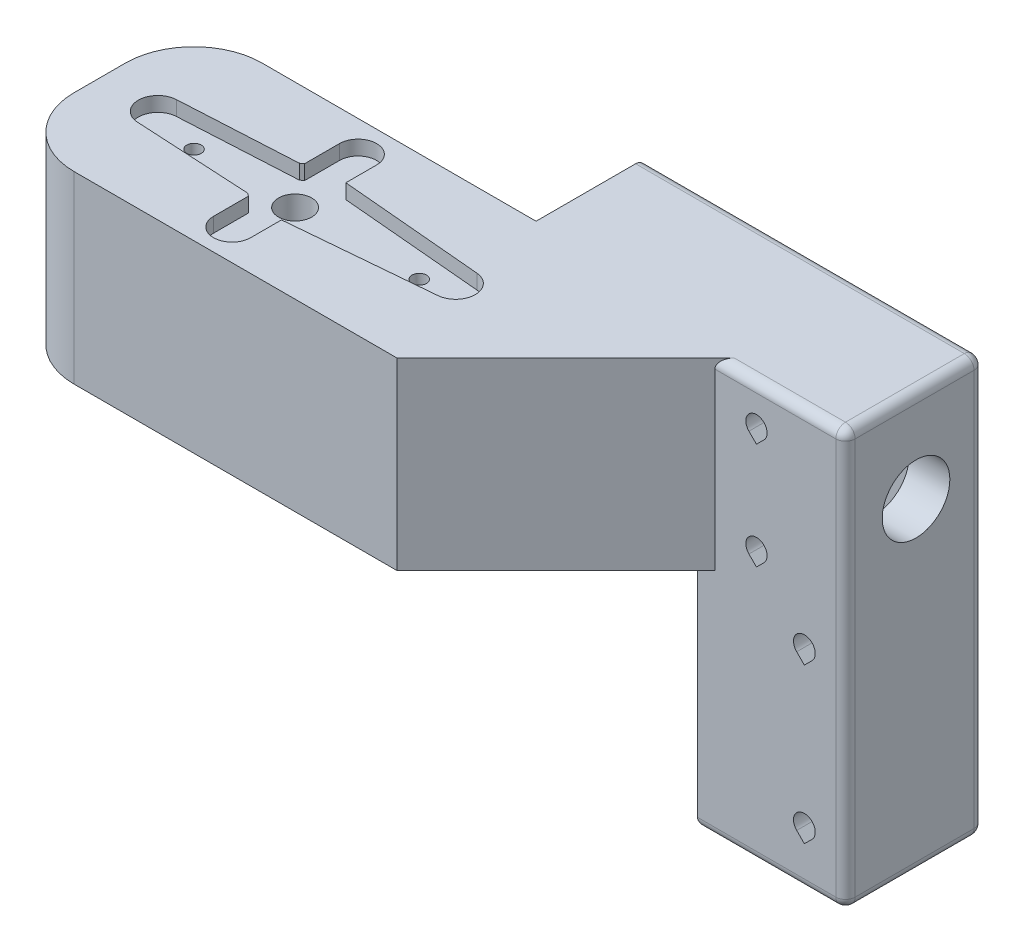
SolidWorks part; units mm, degrees
material "PVC Rígido"
ref_plane "Plano frontal" through (0, 0, 0) normal (0, 0, 1) x (1, 0, 0)
ref_plane "Plano superior" through (0, 0, 0) normal (0, 1, 0) x (1, 0, 0)
ref_plane "Plano direito" through (0, 0, 0) normal (1, 0, 0) x (0, 0, -1)
sketch "Esboço1" plane through (0, 0, 0) normal (0, 1, 0) x (1, 0, 0)
  line L0 (0, 0) -> (-14.05, 0) construction
  line L1 (-14.1591, 1.997) -> (-2.2091, 2.65)
  line L2 (-2.2091, -2.65) -> (-14.1591, -1.997)
  arc A0 (-2.2091, -2.65) -> (-2.2091, 2.65) centre (0, 0) ccw
  arc A1 (-14.1591, 1.997) -> (-14.1591, -1.997) centre (-14.05, 0) ccw
  dimension "D1" = 6.9
  dimension "D2" = 4
  dimension "D3" = 19.5
  dimension "D4" = 5.3
extrude "Ressalto-extrusão1" add sketch "Esboço1" against normal blind 1.4
sketch "Esboço2" plane through (0, -1.4, 0) normal (0, -1, 0) x (1, 0, 0)
  arc A0 (-2.2091, -2.65) -> (-2.2091, 2.65) centre (0, 0) ccw construction
  circle A1 centre (0, 0) radius 3.45
extrude "Ressalto-extrusão2" add sketch "Esboço2" along normal offset from surface (2.4 mm away) 3.8 up to face at (-7.242, 0, 0)
hole_wizard "Furo1" positions "Esboço9" profile "Esboço10" legacy end condition through all
sketch "Esboço9" plane through (0, 0, 0) normal (0, 1, 0) x (1, 0, 0)
  line L1 (-14.45, 0) -> (0, 0) construction
  arc A2 (-14.1591, 1.997) -> (-14.1591, -1.997) centre (-14.05, 0) ccw construction
  point P0 (-14.45, 0)
  point P19 (-16.05, 0)
  dimension "D1" = 1.6
sketch "Esboço10" plane through (-14.45, 0, 0) normal (1, 0, 0) x (0, 0, 1)
  line L0 (0, 0) -> (0, 3.8)
  line L1 (0, 3.8) -> (0.6, 3.8)
  line L2 (0.6, 3.8) -> (0.6, 0)
  line L3 (0.6, 0) -> (0, 0)
  line L4 (0, 110) -> (0, -10) construction
  dimension "Diameter" = 1.2
  dimension "Depth" = 3.8
pattern_linear "Padrão linear1" count 6 spacing 2 along (1, 0, 0) of "Furo1"
sketch "Esboço12" plane through (0, 0, 0) normal (0, 1, 0) x (1, 0, 0)
  line L0 (0.3041, 3.4366) -> (16.6263, 1.9922)
  line L1 (16.6263, -1.9922) -> (0.3041, -3.4366)
  arc A0 (-2.2091, -2.65) -> (-2.2091, 2.65) centre (0, 0) ccw construction
  arc A1 (0.3041, -3.4366) -> (0.3041, 3.4366) centre (0, 0) ccw
  arc A2 (16.6263, 1.9922) -> (16.6263, -1.9922) centre (16.45, 0) cw
  arc A3 (-14.1591, 1.997) -> (-14.1591, -1.997) centre (-14.05, 0) ccw construction
  dimension "D1" = 2
  dimension "D2" = 34.5
extrude "Ressalto-extrusão3" add sketch "Esboço12" against normal up to surface (1.4 mm away) up to face at (-12.45, -1.4, 0.6)
hole_wizard "Furo2" positions "Esboço13" profile "Esboço14" legacy end condition through all
sketch "Esboço13" plane through (0, 0, 0) normal (0, 1, 0) x (1, 0, 0)
  line L0 (0, 0) -> (16.85, 0) construction
  arc A0 (16.6263, -1.9922) -> (16.6263, 1.9922) centre (16.45, 0) ccw construction
  point P0 (16.85, 0)
  point P6 (18.45, 0)
  dimension "D1" = 1.6
sketch "Esboço14" plane through (16.85, 0, 0) normal (1, 0, 0) x (0, 0, 1)
  line L0 (0, 0) -> (0, 3.8)
  line L1 (0, 3.8) -> (0.6, 3.8)
  line L2 (0.6, 3.8) -> (0.6, 0)
  line L3 (0.6, 0) -> (0, 0)
  line L4 (0, 110) -> (0, -10) construction
  dimension "Diameter" = 1.2
  dimension "Depth" = 3.8
pattern_linear "Padrão linear2" count 7 spacing 2 along (-1, 0, 0) of "Furo2"
sketch "Esboço16" plane through (0, 0, 0) normal (0, 1, 0) x (1, 0, 0)
  line L0 (0, -6.45) -> (0, 6.45) construction
  line L1 (-1.9, -6.45) -> (-1.9, 6.45)
  line L2 (1.9, -6.45) -> (1.9, 6.45)
  arc A0 (-1.9, -6.45) -> (1.9, -6.45) centre (0, -6.45) ccw
  arc A1 (1.9, 6.45) -> (-1.9, 6.45) centre (0, 6.45) ccw
  point P2 (0, 0)
  dimension "D2" = 16.7
  dimension "D1" = 3.8
extrude "Ressalto-extrusão4" add sketch "Esboço16" against normal up to surface (1.4 mm away) up to face at (14.85, -1.4, 0.6)
hole_wizard "Furo3" positions "Esboço17" profile "Esboço18" legacy end condition through all
sketch "Esboço17" plane through (0, 0, 0) normal (0, 1, 0) x (1, 0, 0)
  point P0 (0, -6.45)
sketch "Esboço18" plane through (0, 0, 6.45) normal (1, 0, 0) x (0, 0, 1)
  line L0 (0, 0) -> (0, 3.8)
  line L1 (0, 3.8) -> (0.6, 3.8)
  line L2 (0.6, 3.8) -> (0.6, 0)
  line L3 (0.6, 0) -> (0, 0)
  line L4 (0, 110) -> (0, -10) construction
  dimension "Diameter" = 1.2
  dimension "Depth" = 3.8
pattern_linear "Padrão linear3" count 2 spacing 2 along (0, 0, -1) of "Furo3"
pattern_circular "PadrãoCircular1" count 2 over 360 about axis through (0, -1.4, 0) along (0, 1, 0) of "Padrão linear3"
hole_wizard "Furo4" positions "Esboço3" profile "Esboço4" legacy
sketch "Esboço3" plane through (0, -3.8, 0) normal (0, -1, 0) x (-1, 0, 0)
  point P0 (0, 0)
sketch "Esboço4" plane through (0, -3.8, 0) normal (1, 0, 0) x (0, 0, -1)
  line L0 (0, 0) -> (0, 2)
  line L1 (0, 2) -> (2.475, 2)
  line L2 (2.475, 2) -> (2.475, 0)
  line L3 (2.475, 0) -> (0, 0)
  line L4 (0, 110) -> (0, -10) construction
  dimension "Diameter" = 4.95
  dimension "Depth" = 2
hole_wizard "Furo5" positions "Esboço5" profile "Esboço6" legacy
sketch "Esboço5" plane through (0, 0, 0) normal (0, 1, 0) x (1, 0, 0)
  point P0 (0, 0)
sketch "Esboço6" plane through (0, 0, 0) normal (1, 0, 0) x (0, 0, 1)
  line L0 (0, 0) -> (0, 1)
  line L1 (0, 1) -> (2.3, 1)
  line L2 (2.3, 1) -> (2.3, 0)
  line L3 (2.3, 0) -> (0, 0)
  line L4 (0, 110) -> (0, -10) construction
  dimension "Diameter" = 4.6
  dimension "Depth" = 1
hole_wizard "Furo6" positions "Esboço7" profile "Esboço8" legacy end condition through all
sketch "Esboço7" plane through (0, 0, 0) normal (0, 1, 0) x (1, 0, 0)
  point P0 (0, 0)
sketch "Esboço8" plane through (0, 0, 0) normal (1, 0, 0) x (0, 0, 1)
  line L0 (0, 0) -> (0, 3.8)
  line L1 (0, 3.8) -> (1.05, 3.8)
  line L2 (1.05, 3.8) -> (1.05, 0)
  line L3 (1.05, 0) -> (0, 0)
  line L4 (0, 110) -> (0, -10) construction
  dimension "Diameter" = 2.1
  dimension "Depth" = 3.8
sketch "Esboço11" plane through (0, -3.8, 0) normal (0, -1, 0) x (1, 0, 0)
  line L0 (-0.0981, 2.4731) -> (0, 2.375)
  line L1 (0, 2.375) -> (0.0981, 2.4731)
  line L2 (0, 0) -> (0, 2.475) construction
  circle A0 centre (0, 0) radius 2.375 construction
  circle A1 centre (0, 0) radius 2.475
  arc A2 (0.0981, 2.4731) -> (-0.0981, 2.4731) centre (0, 0) ccw
  dimension "D3" = 4.75
  dimension "D2" = 0.1
  dimension "D1" = 0
extrude "Ressalto-extrusão5" add sketch "Esboço11" against normal up to surface (2 mm away) up to face at (0, -1.8, 1.05)
pattern_circular "PadrãoCircular2" count 60 over 360 about axis through (0, -1.4, 0) along (0, 1, 0) of "Ressalto-extrusão5"
sketch "Sketch1" plane through (0, 0, 0) normal (0, 1, 0) x (1, 0, 0)
  line L1 (-20, 9.6246) -> (20, 9.6246)
  line L2 (-20, 9.6246) -> (-20, -9.6246)
  line L3 (-20, -9.6246) -> (20, -9.6246)
  line L4 (20, 9.6246) -> (20, -9.6246)
  line L5 (-20, 9.6246) -> (20, -9.6246) construction
  line L6 (-20, -9.6246) -> (20, 9.6246)
  line L8 (-14.1591, -1.997) -> (-2.2091, -2.65)
  line L9 (-2.2091, 2.65) -> (-14.1591, 1.997)
  line L10 (-14.1591, -1.997) -> (-2.2091, -2.65)
  line L11 (-2.2091, 2.65) -> (-14.1591, 1.997)
  line L12 (1.9, -3.2953) -> (16.6263, -1.9922)
  line L13 (1.9, -6.45) -> (1.9, -3.2953)
  line L14 (-1.9, -2.8797) -> (-1.9, -6.45)
  line L15 (-1.9, 6.45) -> (-1.9, 2.8797)
  line L16 (1.9, 3.2953) -> (1.9, 6.45)
  line L17 (16.6263, 1.9922) -> (1.9, 3.2953)
  line L18 (1.9, -3.2953) -> (16.6263, -1.9922)
  line L19 (1.9, -6.45) -> (1.9, -3.2953)
  line L20 (-1.9, -2.8797) -> (-1.9, -6.45)
  line L21 (-1.9, 6.45) -> (-1.9, 2.8797)
  line L22 (1.9, 3.2953) -> (1.9, 6.45)
  line L23 (16.6263, 1.9922) -> (1.9, 3.2953)
  circle A0 centre (0, 0) radius 3.45 construction
  circle A1 centre (0, 0) radius 3.45
  arc A2 (-2.2091, 2.65) -> (-2.2091, -2.65) centre (0, 0) ccw
  arc A3 (-14.1591, 1.997) -> (-14.1591, -1.997) centre (-14.05, 0) ccw
  arc A4 (-1.9, -6.45) -> (1.9, -6.45) centre (0, -6.45) ccw
  arc A5 (-1.9, -2.8797) -> (-1.9, 2.8797) centre (0, 0) ccw
  arc A6 (1.9, 6.45) -> (-1.9, 6.45) centre (0, 6.45) ccw
  arc A7 (16.6263, -1.9922) -> (16.6263, 1.9922) centre (16.45, 0) ccw
  arc A8 (-1.9, -6.45) -> (1.9, -6.45) centre (0, -6.45) ccw
  arc A9 (-1.9, -2.8797) -> (-1.9, 2.8797) centre (0, 0) ccw
  arc A10 (1.9, 6.45) -> (-1.9, 6.45) centre (0, 6.45) ccw
  arc A11 (16.6263, -1.9922) -> (16.6263, 1.9922) centre (16.45, 0) ccw
  arc A12 (-2.2091, 2.65) -> (-2.2091, -2.65) centre (0, 0) ccw
  arc A13 (-14.1591, 1.997) -> (-14.1591, -1.997) centre (-14.05, 0) ccw
  circle A14 centre (16.85, 0) radius 0.6 construction
  circle A15 centre (14.85, 0) radius 0.6 construction
  circle A16 centre (12.85, 0) radius 0.6 construction
  circle A17 centre (10.85, 0) radius 0.6 construction
  circle A18 centre (8.85, 0) radius 0.6 construction
  circle A19 centre (6.85, 0) radius 0.6 construction
  circle A20 centre (4.85, 0) radius 0.6 construction
  circle A21 centre (-4.45, 0) radius 0.6 construction
  circle A22 centre (-6.45, 0) radius 0.6 construction
  circle A23 centre (-8.45, 0) radius 0.6 construction
  circle A24 centre (-10.45, 0) radius 0.6 construction
  circle A25 centre (-12.45, 0) radius 0.6 construction
  circle A26 centre (-14.45, 0) radius 0.6 construction
  circle A27 centre (16.85, 0) radius 0.6
  circle A28 centre (14.85, 0) radius 0.6
  circle A29 centre (12.85, 0) radius 0.6
  circle A30 centre (10.85, 0) radius 0.6
  circle A31 centre (8.85, 0) radius 0.6
  circle A32 centre (6.85, 0) radius 0.6
  circle A33 centre (4.85, 0) radius 0.6
  circle A34 centre (-4.45, 0) radius 0.6
  circle A35 centre (-6.45, 0) radius 0.6
  circle A36 centre (-8.45, 0) radius 0.6
  circle A37 centre (-10.45, 0) radius 0.6
  circle A38 centre (-12.45, 0) radius 0.6
  circle A39 centre (-14.45, 0) radius 0.6
  point P0 (0, 0)
  dimension "D3" = 40
  dimension "D1" = 0
  dimension "D2" = 0
extrude "Boss-Extrude1" add sketch "Sketch1" along normal blind 4 separate body contours L1 L5 L11 A1 L21 A10 L22 L23 L6 | L5 L2 L6 L10 A13 L11 | L5 L18 L19 A8 L20 A1 L10 L6 L3 | L18 L5 L4 L6 L23 A11 region at (-12.6906, 0, -5.8375) region at (0, 0, -9.2183) region at (19.7624, 0, 0) region at (-12.409, 0, 6.4225)
fillet "Fillet1" radius 7 2 edges at (-20, 2, 9.6246) (-20, 2, -9.6246)
sketch "Sketch2" plane through (0, 0, 0) normal (0, -1, 0) x (1, 0, 0)
  line L0 (-14.1591, 1.997) -> (-2.2091, 2.65) construction
  line L2 (-2.2091, -2.65) -> (-14.1591, -1.997) construction
  line L4 (-1.9, -6.45) -> (-1.9, -2.8797) construction
  line L7 (-1.9, 2.8797) -> (-1.9, 6.45) construction
  line L8 (1.9, 6.45) -> (1.9, 3.2953) construction
  line L9 (1.9, 3.2953) -> (16.6263, 1.9922) construction
  line L10 (16.6263, -1.9922) -> (1.9, -3.2953) construction
  line L11 (1.9, -3.2953) -> (1.9, -6.45) construction
  line L12 (-1.9, 2.8797) -> (-1.9, 6.45)
  line L13 (1.9, 6.45) -> (1.9, 3.2953)
  line L14 (1.9, 3.2953) -> (16.6263, 1.9922)
  line L15 (16.6263, -1.9922) -> (1.9, -3.2953)
  line L16 (1.9, -3.2953) -> (1.9, -6.45)
  line L17 (-1.9, -6.45) -> (-1.9, -2.8797)
  line L18 (-2.2091, -2.65) -> (-14.1591, -1.997)
  line L19 (-14.1591, 1.997) -> (-2.2091, 2.65)
  arc A0 (-14.1591, 1.997) -> (-14.1591, -1.997) centre (-14.05, 0) ccw construction
  arc A3 (-1.9, 2.8797) -> (-2.2091, 2.65) centre (0, 0) ccw construction
  arc A4 (1.9, 6.45) -> (-1.9, 6.45) centre (0, 6.45) ccw construction
  arc A5 (16.6263, -1.9922) -> (16.6263, 1.9922) centre (16.45, 0) ccw construction
  arc A6 (-1.9, -6.45) -> (1.9, -6.45) centre (0, -6.45) ccw construction
  arc A7 (-2.2091, -2.65) -> (-1.9, -2.8797) centre (0, 0) ccw construction
  arc A8 (-1.9, 2.8797) -> (-2.2091, 2.65) centre (0, 0) ccw
  arc A9 (1.9, 6.45) -> (-1.9, 6.45) centre (0, 6.45) ccw
  arc A10 (16.6263, -1.9922) -> (16.6263, 1.9922) centre (16.45, 0) ccw
  arc A11 (-1.9, -6.45) -> (1.9, -6.45) centre (0, -6.45) ccw
  arc A12 (-2.2091, -2.65) -> (-1.9, -2.8797) centre (0, 0) ccw
  arc A13 (-14.1591, 1.997) -> (-14.1591, -1.997) centre (-14.05, 0) ccw
  circle A14 centre (0, 0) radius 1.7
  dimension "D1" = 3.4
extrude "Boss-Extrude2" add sketch "Sketch2" against normal blind 2.5
scale "Scale1" bodies to scale 131 scale about centroid uniform scaling yes scale factor 1.01
sketch "Sketch3" plane through (0, -0.0186, 0) normal (0, -1, 0) x (1, 0, 0)
  circle A0 centre (-0.0045, 0) radius 6.95
  dimension "D1" = 13.9
sketch "Sketch4" plane through (0, 2.5064, 0) normal (0, 1, 0) x (1, 0, 0)
  circle A0 centre (-10.455, 0) radius 0.75
  arc A1 (-14.3052, 2.017) -> (-14.3052, -2.017) centre (-14.195, 0) ccw construction
  circle A2 centre (12.84, 0) radius 0.75
  arc A3 (16.7881, -2.0121) -> (16.7881, 2.0121) centre (16.61, 0) ccw construction
  point P5 (-16.215, 0)
  point P11 (18.63, 0)
  dimension "D2" = 1.5
  dimension "D4" = 1.5
  dimension "D1" = 5.76
  dimension "D3" = 5.79
extrude "Cut-Extrude1" cut sketch "Sketch4" against normal up to next (2.525 mm away)
sketch "Sketch6" plane through (0, -0.0186, 0) normal (0, -1, 0) x (1, 0, 0)
  line L4 (-13.1345, -9.7209) -> (20.1955, -9.7209)
  line L5 (20.1955, -9.7209) -> (20.1955, 9.7209)
  line L6 (20.1955, 9.7209) -> (-13.1345, 9.7209)
  line L7 (-20.2045, 2.6509) -> (-20.2045, -2.6509)
  line L8 (-13.1345, -9.7209) -> (20.1955, -9.7209)
  line L9 (20.1955, -9.7209) -> (20.1955, 9.7209)
  line L10 (20.1955, 9.7209) -> (-13.1345, 9.7209)
  line L11 (-20.2045, 2.6509) -> (-20.2045, -2.6509)
  circle A0 centre (12.84, 0) radius 0.75 construction
  circle A1 centre (-10.455, 0) radius 0.75 construction
  circle A2 centre (12.84, 0) radius 0.75
  circle A3 centre (-10.455, 0) radius 0.75
  arc A14 (-13.1345, 9.7209) -> (-20.2045, 2.6509) centre (-13.1345, 2.6509) ccw
  arc A15 (-13.1345, 9.7209) -> (-20.2045, 2.6509) centre (-13.1345, 2.6509) ccw
  arc A16 (-20.2045, -2.6509) -> (-13.1345, -9.7209) centre (-13.1345, -2.6509) ccw
  arc A17 (-20.2045, -2.6509) -> (-13.1345, -9.7209) centre (-13.1345, -2.6509) ccw
  dimension "D1" = 0
extrude "Boss-Extrude5" add sketch "Sketch6" along normal blind 15
sketch "Sketch7" plane through (20.1955, 0, 0) normal (1, 0, 0) x (0, 0, -1)
  line L0 (0, 4.0214) -> (0, -15.0186) construction
  line L1 (9.7209, 4.0214) -> (-9.7209, 4.0214) construction
  line L2 (9.7209, -15.0186) -> (-9.7209, -15.0186) construction
  line L4 (9.7209, 4.0214) -> (6.7209, 4.0214)
  line L5 (9.7209, 4.0214) -> (9.7209, -15.0186)
  line L6 (9.7209, -15.0186) -> (6.7209, -15.0186)
  line L7 (6.7209, 4.0214) -> (6.7209, -15.0186)
  dimension "D1" = 3
extrude "Boss-Extrude6" add sketch "Sketch7" along normal blind 30
sketch "Sketch8" plane through (0, 0, -9.7209) normal (0, 0, -1) x (-1, 0, 0)
  line L0 (13.1345, -15.0186) -> (-50.1955, -15.0186) construction
  line L1 (-50.1955, 4.0214) -> (-15.1955, 4.0214)
  line L2 (-50.1955, 4.0214) -> (-50.1955, -15.0186)
  line L3 (-50.1955, -15.0186) -> (-15.1955, -15.0186)
  line L4 (-15.1955, 4.0214) -> (-15.1955, -15.0186)
  dimension "D1" = 35
extrude "Boss-Extrude7" add sketch "Sketch8" along normal blind 11.2941
sketch "Sketch9" plane through (50.1955, 0, 0) normal (1, 0, 0) x (0, 0, -1)
  line L1 (21.015, -5.4986) -> (8.015, -5.4986) construction
  line L5 (21.015, 4.0214) -> (21.015, -15.0186) construction
  circle A1 centre (14.0164, -5.4986) radius 3.4986
  point P4 (10.5177, -5.4986)
  point P5 (17.515, -5.4986)
  dimension "D1" = 13
  dimension "D2" = 2.5028
  dimension "D3" = 3.5
extrude "Cut-Extrude2" cut sketch "Sketch9" against normal up to next (35 mm away)
sketch "Sketch10" plane through (15.1955, 0, 0) normal (-1, 0, 0) x (0, 0, 1)
  line L0 (-21.015, -5.4986) -> (-8.015, -5.4986) construction
  line L1 (-9.7209, 2.7955) -> (-19.3091, 2.7955)
  line L2 (-19.3091, 2.7955) -> (-19.3091, -13.7927)
  line L3 (-21.015, -15.0186) -> (-21.015, 4.0214) construction
  line L4 (-9.7209, -13.7927) -> (-19.3091, -13.7927)
  line L12 (-9.7209, -13.7927) -> (-9.7209, 2.7955)
  point P4 (-9.7209, -5.4986)
  point P10 (-19.3091, -5.4986)
  dimension "D1" = 13
  dimension "D2" = 1.7059
extrude "Cut-Extrude3" cut sketch "Sketch10" against normal blind 30.7941
chamfer "Chamfer2" distance 16.5 angle 45 1 edges at (20.1955, -5.4986, -6.7209)
sketch "Sketch11" plane through (0, 0, -9.7209) normal (0, 0, -1) x (-1, 0, 0)
  line L0 (-15.1955, 2.7955) -> (-15.1955, -13.7927)
  line L1 (-45.9896, -5.4986) -> (-15.1955, -5.4986) construction
  line L2 (-40.9896, 0.0015) -> (-40.9896, -13.219) construction
  line L3 (-41.7674, -0.7763) -> (-40.9896, -1.5542)
  line L4 (-40.9896, -1.5542) -> (-40.2118, -0.7763)
  line L5 (-41.7674, -11.7765) -> (-40.9896, -12.5543)
  line L6 (-40.2118, -11.7765) -> (-40.9896, -12.5543)
  line L7 (-29.9896, -2.9586) -> (-29.9896, -10.1409) construction
  line L8 (-15.1955, -13.7927) -> (-15.1955, -15.0186)
  line L9 (-15.1955, -15.0186) -> (13.1345, -15.0186)
  line L10 (13.1345, -15.0186) -> (13.1345, 4.0214)
  line L11 (13.1345, 4.0214) -> (-15.1955, 4.0214)
  line L12 (-15.1955, 4.0214) -> (-15.1955, 2.7955)
  line L13 (-15.1955, 2.7955) -> (-45.9896, 2.7955)
  line L14 (-45.9896, 2.7955) -> (-45.9896, -13.7927)
  line L15 (-45.9896, -13.7927) -> (-15.1955, -13.7927)
  line L16 (-15.1955, -13.7927) -> (-15.1955, -15.0186)
  line L17 (-15.1955, -15.0186) -> (13.1345, -15.0186)
  line L18 (13.1345, -15.0186) -> (13.1345, 4.0214)
  line L19 (13.1345, 4.0214) -> (-15.1955, 4.0214)
  line L20 (-15.1955, 4.0214) -> (-15.1955, 2.7955)
  line L21 (-15.1955, 2.7955) -> (-45.9896, 2.7955)
  line L22 (-45.9896, 2.7955) -> (-45.9896, -13.7927)
  line L23 (-45.9896, -13.7927) -> (-15.1955, -13.7927)
  line L24 (-29.6361, -3.3122) -> (-29.9896, -3.6657)
  line L25 (-29.6361, -5.8522) -> (-29.9896, -6.2057)
  line L26 (-29.6361, -8.3922) -> (-29.9896, -8.7457)
  line L27 (-30.3432, -8.3922) -> (-29.9896, -8.7457)
  line L28 (-30.3432, -5.8522) -> (-29.9896, -6.2057)
  line L29 (-30.3432, -3.3122) -> (-29.9896, -3.6657)
  arc A0 (-40.2118, -0.7763) -> (-41.7674, -0.7763) centre (-40.9896, 0.0015) ccw
  arc A1 (-41.7674, -11.7765) -> (-40.2118, -11.7765) centre (-40.9896, -10.9987) cw
  arc A2 (-29.6361, -3.3122) -> (-30.3432, -3.3122) centre (-29.9896, -2.9586) ccw
  arc A3 (-29.6361, -5.8522) -> (-30.3432, -5.8522) centre (-29.9896, -5.4986) ccw
  arc A4 (-29.6361, -8.3922) -> (-30.3432, -8.3922) centre (-29.9896, -8.0386) ccw
  dimension "D3" = 5
  dimension "D4" = 2.2
  dimension "D7" = 1
  dimension "D2" = 2.794
  dimension "D5" = 11
  dimension "D6" = 2.54
  dimension "D9" = 45
  dimension "D10" = 45
  dimension "D11" = 45
  dimension "D12" = 45
  dimension "D13" = 45
  dimension "D1" = 0
  dimension "D8" = 3
extrude "Cut-Extrude4" cut sketch "Sketch11" against normal blind 3 contours A1 | A0 | A3 L28 L25 | A4 L27 L26 | A2 L29 L24 region at (40.9896, -0.0758, -9.7209) region at (40.9896, -11.0759, -9.7209)
sketch "Sketch14" plane through (0, -15.0186, 0) normal (0, -1, 0) x (1, 0, 0)
  line L0 (45.9896, -9.7209) -> (15.1955, -9.7209) construction
  line L1 (45.9896, -9.7209) -> (34.8955, -9.7209)
  line L2 (45.9896, -9.7209) -> (50.1955, -9.7209)
  line L3 (50.1955, -6.7209) -> (50.1955, -21.015) construction
  line L4 (50.1955, -9.7209) -> (50.1955, -6.7209)
  line L5 (50.1955, -6.7209) -> (34.8955, -6.7209)
  line L6 (34.8955, -6.7209) -> (34.8955, -9.7209)
  dimension "D1" = 15.3
extrude "Boss-Extrude8" add sketch "Sketch14" along normal blind 24
sketch "Sketch15" plane through (0, 0, -9.7209) normal (0, 0, -1) x (-1, 0, 0)
  line L0 (-50.1955, -39.0186) -> (-50.1955, -15.0186) construction
  line L1 (-34.8955, -15.0186) -> (-50.1955, -15.0186) construction
  line L2 (-45.9455, -17.2686) -> (-45.9455, -34.8596) construction
  line L3 (-45.15, -18.0641) -> (-45.9455, -18.8596)
  line L4 (-48.1955, -15.0186) -> (-35.1288, -15.0186)
  line L5 (-48.1955, -15.0186) -> (-48.1955, -35.5186)
  line L6 (-48.1955, -35.5186) -> (-35.1288, -35.5186)
  line L8 (-46.741, -34.0641) -> (-45.9455, -34.8596)
  line L9 (-45.15, -34.0641) -> (-45.9455, -34.8596)
  line L10 (-46.741, -18.0641) -> (-45.9455, -18.8596)
  arc A0 (-45.15, -18.0641) -> (-46.741, -18.0641) centre (-45.9455, -17.2686) ccw
  arc A2 (-46.741, -34.0641) -> (-45.15, -34.0641) centre (-45.9455, -33.2686) cw
  dimension "D8" = 2.25
  dimension "D9" = 2.25
  dimension "D1" = 20.5
  dimension "D2" = 2.25
  dimension "D3" = 2.25
  dimension "D4" = 2
  dimension "D5" = 0
  dimension "D6" = 2.25
  dimension "D7" = 2.25
  dimension "D10" = 45
  dimension "D11" = 45
sketch "Sketch16" plane through (0, 0, -9.7209) normal (0, 0, -1) x (-1, 0, 0)
  line L0 (-34.8955, -39.0186) -> (-50.1955, -39.0186) construction
  line L1 (-50.1955, -15.0186) -> (-48.6955, -15.0186)
  line L2 (-50.1955, -15.0186) -> (-50.1955, -39.0186)
  line L3 (-50.1955, -39.0186) -> (-48.6955, -39.0186)
  line L4 (-48.6955, -15.0186) -> (-48.6955, -39.0186)
  line L6 (-34.8955, -39.0186) -> (-48.6955, -39.0186)
  line L7 (-34.8955, -39.0186) -> (-34.8955, -37.0186)
  line L8 (-34.8955, -37.0186) -> (-48.6955, -37.0186)
  line L9 (-48.6955, -39.0186) -> (-48.6955, -37.0186)
  line M7 (-50.1955, -39.0186) -> (-34.8955, -39.0186)
  line M8 (-34.8955, -39.0186) -> (-34.8955, -15.0186)
  dimension "D1" = 1.5
  dimension "D2" = 2
extrude "Boss-Extrude9" add sketch "Sketch16" along normal up to surface (11.2941 mm away) contours L8 L4 M8 M7 | L4 L1 L2 L3 region at (41.7955, -38.0186, -9.7209) up to face at (32.6955, -5.4986, -21.015)
sketch "Sketch17" plane through (0, -15.0186, 0) normal (0, -1, 0) x (1, 0, 0)
  line L0 (34.8955, -21.015) -> (48.6955, -21.015) construction
  line L1 (34.8955, -21.015) -> (48.6955, -21.015)
  line L2 (34.8955, -21.015) -> (48.6955, -21.015)
  line L3 (34.8955, -21.015) -> (34.8955, -19.015)
  line L4 (34.8955, -19.015) -> (48.6955, -19.015)
  line L10 (15.1955, -21.015) -> (48.6955, -21.015)
  line L11 (48.6955, -21.015) -> (48.6955, -9.7209)
  line L12 (48.6955, -9.7209) -> (34.8955, -9.7209)
  line L13 (34.8955, -9.7209) -> (34.8955, -6.7209)
  line L14 (34.8955, -6.7209) -> (36.6955, -6.7209)
  line L15 (36.6955, -6.7209) -> (20.2538, 9.7209)
  line L16 (20.2538, 9.7209) -> (-13.1345, 9.7209)
  line L17 (-20.2045, 2.6509) -> (-20.2045, -2.6509)
  line L18 (-13.1345, -9.7209) -> (15.1955, -9.7209)
  line L19 (15.1955, -9.7209) -> (15.1955, -21.015)
  line L20 (15.1955, -21.015) -> (48.6955, -21.015)
  line L21 (48.6955, -21.015) -> (48.6955, -9.7209)
  line L22 (48.6955, -9.7209) -> (34.8955, -9.7209)
  line L23 (34.8955, -9.7209) -> (34.8955, -6.7209)
  line L24 (34.8955, -6.7209) -> (36.6955, -6.7209)
  line L25 (36.6955, -6.7209) -> (20.2538, 9.7209)
  line L26 (20.2538, 9.7209) -> (-13.1345, 9.7209)
  line L27 (-20.2045, 2.6509) -> (-20.2045, -2.6509)
  line L28 (-13.1345, -9.7209) -> (15.1955, -9.7209)
  line L29 (15.1955, -9.7209) -> (15.1955, -21.015)
  arc A2 (-13.1345, 9.7209) -> (-20.2045, 2.6509) centre (-13.1345, 2.6509) ccw
  arc A3 (-20.2045, -2.6509) -> (-13.1345, -9.7209) centre (-13.1345, -2.6509) ccw
  arc A4 (-13.1345, 9.7209) -> (-20.2045, 2.6509) centre (-13.1345, 2.6509) ccw
  arc A5 (-20.2045, -2.6509) -> (-13.1345, -9.7209) centre (-13.1345, -2.6509) ccw
  line M17 (15.1955, -21.015) -> (48.6955, -21.015)
  line M18 (48.6955, -21.015) -> (48.6955, -9.7209)
  dimension "D2" = 2
  dimension "D1" = 0
extrude "Boss-Extrude10" add sketch "Sketch17" along normal up to surface (22 mm away) contours L4 L3 M17 M18 region at (41.7955, -15.0186, -20.015) up to face at (41.7955, -37.0186, -15.3679)
fillet "Fillet2" radius 1 9 edges at (43.4455, 4.0214, -6.7209) (34.8955, -39.0186, -13.8679) (50.1955, -39.0186, -13.8679) (50.1955, -17.4986, -21.015) (50.1955, 4.0214, -13.8679) (50.1955, -17.4986, -6.7209) (32.6955, 4.0214, -21.015) (42.5455, -39.0186, -21.015) (42.5455, -39.0186, -6.7209)
extrude "Cut-Extrude8" cut sketch "Sketch15" against normal blind 10 contours A2 L9 L8 | A0 L10 L3
extrude "Cut-Extrude17" cut sketch "Sketch3" along normal up to next (15 mm away)
